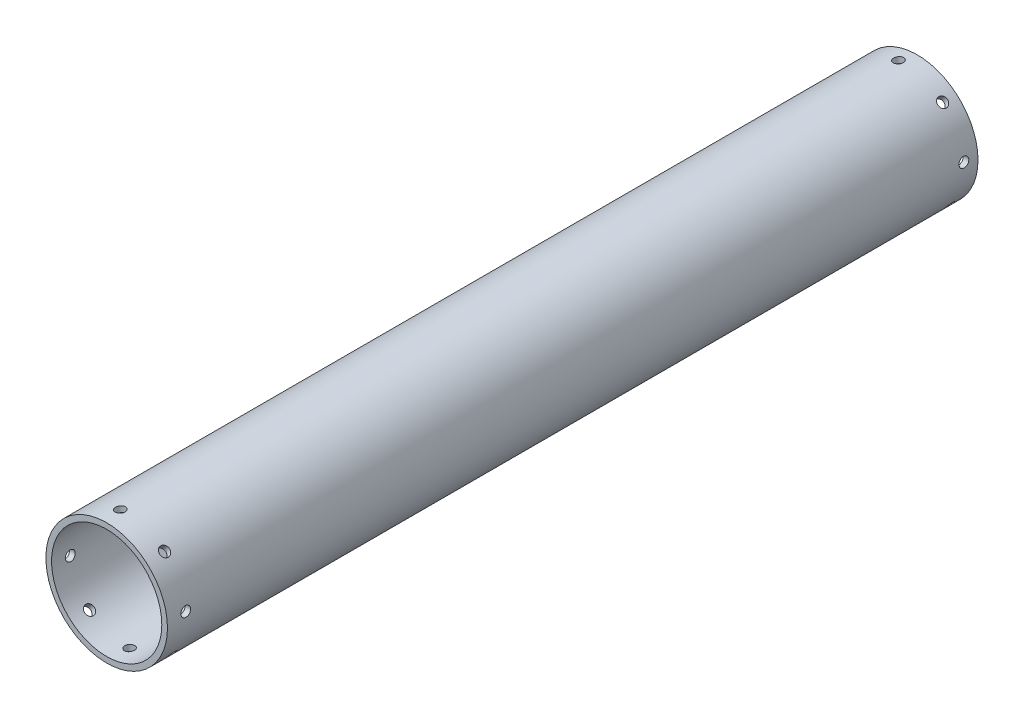
SolidWorks part; units mm, degrees
note: '?' marks a value the reader was unsure of.
ref_plane "Front Plane" through (0, 0, 0) normal (0, 0, 1) x (1, 0, 0)
ref_plane "Top Plane" through (0, 0, 0) normal (0, 1, 0) x (1, 0, 0)
ref_plane "Right Plane" through (0, 0, 0) normal (1, 0, 0) x (0, 0, -1)
sketch "Sketch1" plane through (0, 0, 0) normal (0, 0, 1) x (1, 0, 0)
  circle A0 centre (0, 0) radius 37.5
  circle A1 centre (0, 0) radius 34
  dimension "D1" = 75
  dimension "D2" = 68
extrude "Boss-Extrude1" add sketch "Sketch1" along normal blind 500
hole_wizard "1/4 (0.236) Diameter Hole1" positions "3DSketch2" profile "Sketch4" hole size "1/4" standard "ANSI Inch"
sketch3d "3DSketch2"
  point P0 (-3.0322, 37.3772, 488.5629)
  point P6 (11.2197, -65.3586, 0)
  dimension "D1" = 490
sketch "Sketch4" plane through (-3.0322, 37.3772, 488.5629) normal (0, 0, 1) x (-0.9967, -0.0809, 0)
  line L0 (0, 0) -> (0, 6.1)
  line L1 (0, 6.1) -> (2.9972, 4.2991)
  line L2 (2.9972, 4.2991) -> (2.9972, 0)
  line L5 (2.9972, 0) -> (0, 0)
  line L10 (0, 6.1) -> (-2.9972, 4.2991) construction
  line L11 (0, -6.35) -> (0, 107.95) construction
  dimension "Hole Dia." = 5.9944
  dimension "Hole Depth" = 6.1
  dimension "Drill Angle" = 118
pattern_circular "CirPattern1" count 8 over 360 about axis through (0, 0, 500) along (0, 0, -1) of "1/4 (0.236) Diameter Hole1"
ref_plane "Plane1" through (0, 0, 570) normal (0, 0, 1) x (1, 0, 0)
ref_axis "Axis1" through (0, 0, 500) along (0, 0, -1)?
pattern_linear "LPattern1" count 2 spacing 480 along (0, 0, -1) of "CirPattern1", "1/4 (0.236) Diameter Hole1"
